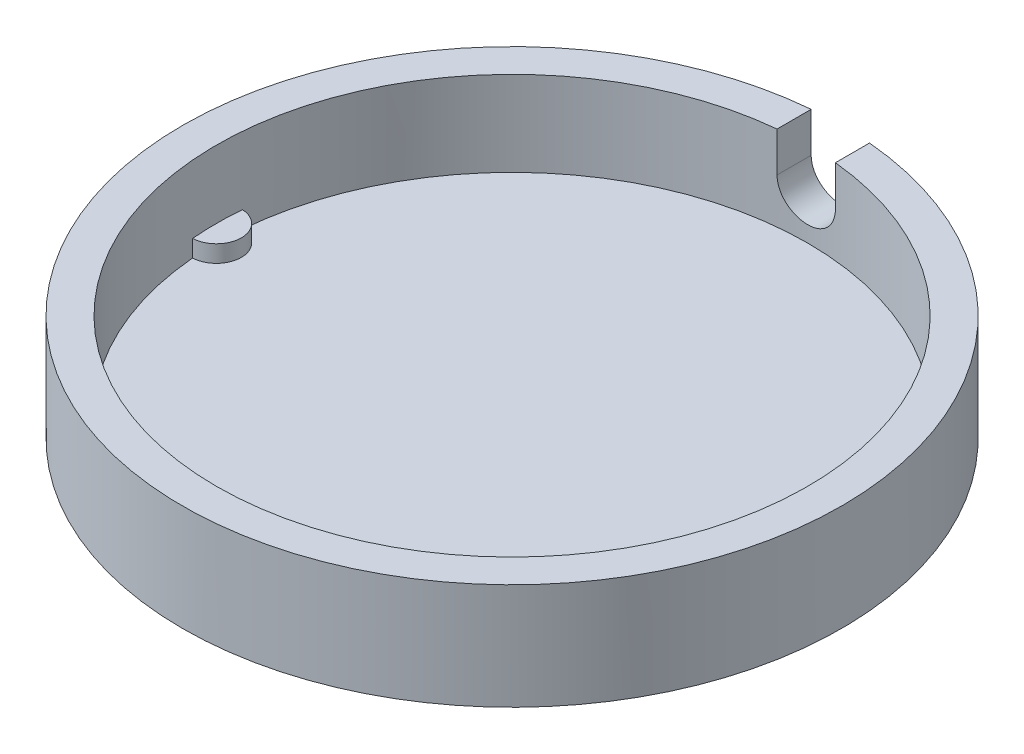
SolidWorks part; units mm, degrees
ref_plane "Front Plane" through (0, 0, 0) normal (0, 0, 1) x (1, 0, 0)
ref_plane "Top Plane" through (0, 0, 0) normal (0, 1, 0) x (1, 0, 0)
ref_plane "Right Plane" through (0, 0, 0) normal (1, 0, 0) x (0, 0, -1)
sketch "Sketch1" plane through (0, 0, 0) normal (0, 1, 0) x (1, 0, 0)
  circle A0 centre (0, 0) radius 31.06
  dimension "D1" = 62.12
extrude "Boss-Extrude1" add sketch "Sketch1" along normal blind 10
sketch "Sketch2" plane through (0, 10, 0) normal (0, 1, 0) x (1, 0, 0)
  circle A0 centre (0, 0) radius 27.86
  circle A1 centre (0, 0) radius 31.06 construction
  circle A2 centre (0, 0) radius 31.06
  dimension "D1" = 3.2
extrude "Cut-Extrude1" cut sketch "Sketch2" against normal blind 8 contours A0 region at (0, 10, 0)
sketch "Sketch3" plane through (0, 2, 0) normal (0, 1, 0) x (1, 0, 0)
  arc A0 (-27.7609, -2.3479) -> (-27.7609, 2.3479) centre (-27.86, 0) ccw
  circle A1 centre (0, 0) radius 27.86 construction
  arc A2 (27.7609, 2.3479) -> (27.7609, -2.3479) centre (27.86, 0) ccw
  arc A3 (27.7609, -2.3479) -> (27.7609, 2.3479) centre (0, 0) ccw
  arc A4 (-27.7609, 2.3479) -> (-27.7609, -2.3479) centre (0, 0) ccw
  dimension "D1" = 4.7
  dimension "D2" = 4.7
extrude "Boss-Extrude2" add sketch "Sketch3" along normal blind 1.6
sketch "Sketch4" plane through (0, 0, 0) normal (0, 0, 1) x (1, 0, 0)
  line L0 (27.7609, 2) -> (-27.7609, 2) construction
  line L1 (27.7609, 2) -> (-27.7609, 2)
  line L2 (0, 0) -> (0, 4.7714)
  line L3 (27.86, 10) -> (-27.86, 10) construction
  line L4 (27.86, 10) -> (-27.86, 10)
  line L5 (-2.75, 6.25) -> (-2.75, 10)
  line L6 (2.75, 6.25) -> (2.75, 10)
  circle A0 centre (0, 6.25) radius 2.75
  dimension "D1" = 5.5
  dimension "D2" = 4.25
extrude "Cut-Extrude2" cut sketch "Sketch4" against normal through all contours A0 L6 L4 L5 | A0 region at (0, 9.0865, 0)
